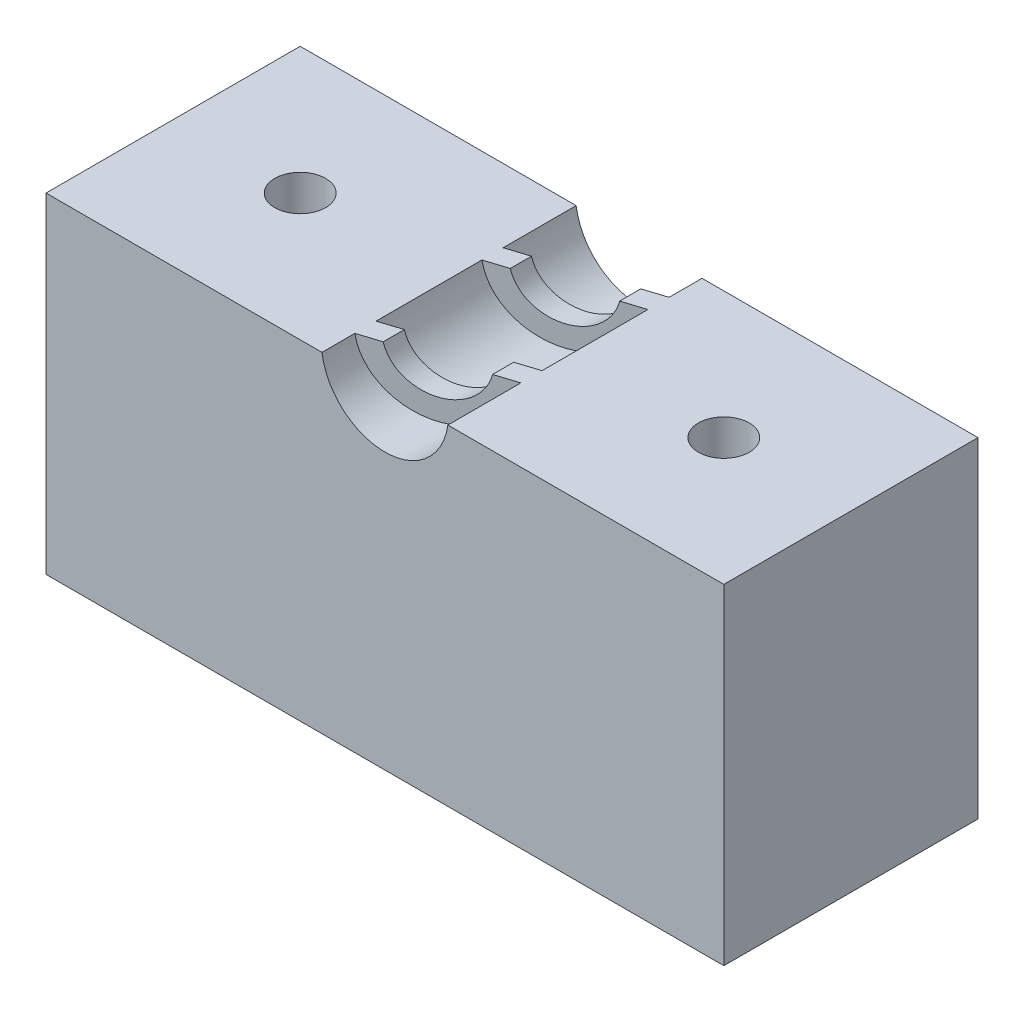
SolidWorks part; units mm, degrees
ref_plane "前视基准面" through (0, 0, 0) normal (0, 0, 1) x (1, 0, 0)
ref_plane "上视基准面" through (0, 0, 0) normal (0, 1, 0) x (1, 0, 0)
ref_plane "右视基准面" through (0, 0, 0) normal (1, 0, 0) x (0, 0, -1)
other "Configuration Table"
sketch "草图1" plane through (0, 0, 0) normal (0, 0, 1) x (1, 0, 0)
  line L1 (-8, -8) -> (8, -8)
  line L2 (-8, -8) -> (-8, 8)
  line L3 (-8, 8) -> (8, 8)
  line L4 (8, -8) -> (8, 8)
  line L5 (-8, -8) -> (8, 8) construction
  line L6 (-8, 8) -> (8, -8) construction
  circle A0 centre (0, 0) radius 1.5
  point P0 (0, 0)
  dimension "D3" = 3
  dimension "D1" = 16
  dimension "D2" = 16
extrude "凸台-拉伸1" add sketch "草图1" along normal mid plane 6
sketch "草图2" plane through (0, 0, 3) normal (0, 0, 1) x (1, 0, 0)
  circle A0 centre (0, 0) radius 1.5 construction
  circle A1 centre (0, 0) radius 1.5
curve "螺旋线/涡状线1" [suppressed] pitch 3 height 6 turns 2
sketch "草图4" [suppressed] plane through (0, 0, 0) normal (0, 1, 0) x (1, 0, 0)
  line L0 (0, 4.8801) -> (0, -4.2719) construction
sketch3d "3D草图1" [suppressed]
  spline S0 degree 3 poles (-942.1956, -331.2134, -36.5595) (37.1464, -47.6823, 7.9547) (5.73, 5.65, 5.1859) (-1.0881, 1.0883, 2.625) (-1.4219, 0.589, 2.4375) (-1.539, 0, 2.25) (-1.4219, -0.589, 2.0625) (-1.0883, -1.0883, 1.875) (-0.589, -1.4219, 1.6875) (0, -1.5391, 1.5) (0.589, -1.4219, 1.3125) (1.0883, -1.0883, 1.125) (1.4219, -0.589, 0.9375) (1.5391, 0, 0.75) (1.4219, 0.589, 0.5625) (1.0883, 1.0883, 0.375) (0.589, 1.4219, 0.1875) (0, 1.5391, 0) (-0.589, 1.4219, -0.1875) (-1.0883, 1.0883, -0.375) (-1.4219, 0.589, -0.5625) (-1.5391, 0, -0.75) (-1.4219, -0.589, -0.9375) (-1.0883, -1.0883, -1.125) (-0.589, -1.4219, -1.3125) (0, -1.5391, -1.5) (0.589, -1.4219, -1.6875) (1.0883, -1.0883, -1.875) (1.4219, -0.589, -2.0625) (1.539, 0, -2.25) (1.4219, 0.589, -2.4375) (1.0881, 1.0883, -2.625) (-5.73, 5.65, -5.1859) (-37.1462, -47.6821, -7.9547) (942.1897, -331.2117, 36.5592) knots -1.18812 -1.18812 -1.18812 -1.18812 0.03125 0.0625 0.09375 0.125 0.15625 0.1875 0.21875 0.25 0.28125 0.3125 0.34375 0.375 0.40625 0.4375 0.46875 0.5 0.53125 0.5625 0.59375 0.625 0.65625 0.6875 0.71875 0.75 0.78125 0.8125 0.84375 0.875 0.90625 0.9375 0.96875 2.188117 2.188117 2.188117 2.188117 only from (0, 1.5, 3) to (0, 1.5, -3) construction
  spline S1 degree 3 poles (0, 1.5, 3) (-0.1952, 1.5, 2.9379) (-0.5895, 1.4219, 2.8123) (-1.0881, 1.0883, 2.625) (-1.4219, 0.589, 2.4375) (-1.539, 0, 2.25) (-1.4219, -0.589, 2.0625) (-1.0883, -1.0883, 1.875) (-0.589, -1.4219, 1.6875) (0, -1.5391, 1.5) (0.589, -1.4219, 1.3125) (1.0883, -1.0883, 1.125) (1.4219, -0.589, 0.9375) (1.5391, 0, 0.75) (1.4219, 0.589, 0.5625) (1.0883, 1.0883, 0.375) (0.589, 1.4219, 0.1875) (0, 1.5391, 0) (-0.589, 1.4219, -0.1875) (-1.0883, 1.0883, -0.375) (-1.4219, 0.589, -0.5625) (-1.5391, 0, -0.75) (-1.4219, -0.589, -0.9375) (-1.0883, -1.0883, -1.125) (-0.589, -1.4219, -1.3125) (0, -1.5391, -1.5) (0.589, -1.4219, -1.6875) (1.0883, -1.0883, -1.875) (1.4219, -0.589, -2.0625) (1.539, 0, -2.25) (1.4219, 0.589, -2.4375) (1.0881, 1.0883, -2.625) (0.5895, 1.4219, -2.8123) (0.1952, 1.5, -2.9379) (0, 1.5, -3) knots 0 0 0 0 0.03125 0.0625 0.09375 0.125 0.15625 0.1875 0.21875 0.25 0.28125 0.3125 0.34375 0.375 0.40625 0.4375 0.46875 0.5 0.53125 0.5625 0.59375 0.625 0.65625 0.6875 0.71875 0.75 0.78125 0.8125 0.84375 0.875 0.90625 0.9375 0.96875 1 1 1 1
sketch3d "3D草图2" [suppressed]
  line L0 (0, 1.5, 3) -> (0, 0, 3) construction
  line L1 (0, 0, -4.8801) -> (0, 0, 4.2719) construction
  line L2 (0, 1.5, 3) -> (0, 0.3536, 3)
surface "曲面-扫描1" [suppressed]
thicken "加厚3" [suppressed] surfaces to thicken 107 thickness 0.225 parameters "D1"=0.225
sketch "草图6" plane through (0, 0, 0) normal (0, 1, 0) x (1, 0, 0)
  line L0 (-1.5, -3) -> (1.5, -3) construction
  line L1 (1.5, 3) -> (-1.5, 3) construction
  line L2 (-1.5, -3) -> (1.5, -3)
  line L3 (1.5, 3) -> (-1.5, 3)
  line L4 (-1.5, 3) -> (-1.5, -3)
  line L5 (1.5, -3) -> (1.5, 3)
  line L6 (-1.5, 0.7724) -> (1.5, 1.7276)
  line L7 (1.5, 1.7276) -> (1.5, 2.2276)
  line L8 (1.5, 2.2276) -> (-1.5, 1.2724)
  line L9 (-1.5, -1.7276) -> (1.5, -0.7724)
  line L10 (-1.5, -2.2276) -> (1.5, -1.2724)
  line L11 (-2.0945, -0.6668) -> (3.135, 0.9981) construction
  line L12 (-3.1004, 0) -> (4.2723, 0) construction
  dimension "D1" = 2.5
  dimension "D2" = 0.5
  dimension "D3" = 0.5
  dimension "D4" = 17.66
extrude "凸台-拉伸2" add sketch "草图6" against normal up to surface (8 mm away) contours L4 L10 L5 L9 | L5 L8 L4 L6 region at (0, 0, 1.5) region at (0, 0, -1.5) up to face at (0, -8, 0)
sketch "草图7" plane through (0, 0, 0) normal (0, 0, 1) x (1, 0, 0)
  line L0 (0, 0) -> (-0.979, -0.2039)
  line L1 (0, 0) -> (0.979, -0.2039)
  line L2 (-0.979, -0.2039) -> (-8, -0.2039)
  line L3 (0.979, -0.2039) -> (8, -0.2039)
  line L6 (8, -8) -> (8, 8)
  line L7 (-8, -8) -> (8, -8)
  line L8 (-8, 8) -> (-8, -8)
  line L9 (8, 8) -> (-8, 8)
  line L10 (8, -8) -> (8, 8)
  line L11 (-8, -8) -> (8, -8)
  line L12 (-8, 8) -> (-8, -8)
  line L13 (8, 8) -> (-8, 8)
  circle A0 centre (0, 0) radius 1
  dimension "D1" = 2
  dimension "D2" = 0
  dimension "D3" = 156.47
extrude "切除-拉伸2" cut sketch "草图7" against normal through all both and the other way through all contours A0 L3 L10 L13 L12 L2 | L1 A0 L0 | L0 A0 L1 region at (0, -0.478, 0) region at (0, 0.3675, 0) region at (0, 3.9528, 0)
sketch "草图8" plane through (0, 0, 0) normal (0, 1, 0) x (1, 0, 0)
  line L0 (0, 5.5834) -> (0, -5.0797) construction
  circle A0 centre (-5, 0) radius 0.6
  circle A1 centre (5, 0) radius 0.6
  dimension "D2" = 1.2
  dimension "D3" = 10
extrude "切除-拉伸3" cut sketch "草图8" against normal through all
fillet "圆角1" [suppressed] radius 1
equation "\"x\"=0.8094"
